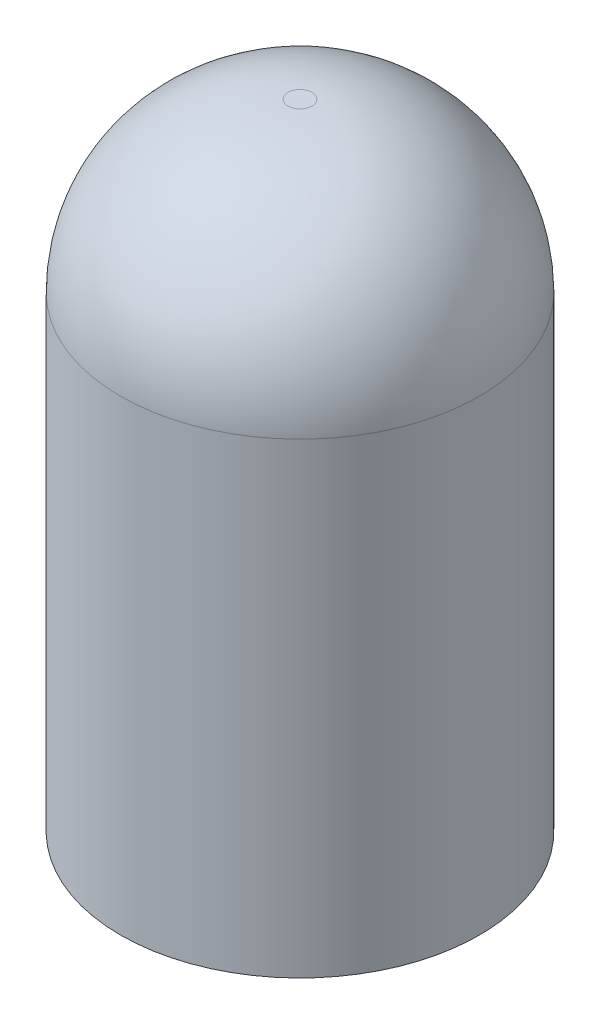
SolidWorks part; units mm, degrees
ref_plane "Front Plane" through (0, 0, 0) normal (0, 0, 1) x (1, 0, 0)
ref_plane "Top Plane" through (0, 0, 0) normal (0, 1, 0) x (1, 0, 0)
ref_plane "Right Plane" through (0, 0, 0) normal (1, 0, 0) x (0, 0, -1)
sketch "Sketch2" plane through (0, 0, 0) normal (0, 1, 0) x (1, 0, 0)
  circle A0 centre (0, 0) radius 1.5
extrude "Boss-Extrude1" add sketch "Sketch2" along normal blind 5.3
fillet "Fillet1" radius 1.4 1 edges at (0, 5.3, 1.5)
sketch "Sketch3" plane through (0, 0, 0) normal (0, 0, 1) x (1, 0, 0)
  line L0 (0, 0) -> (0, 2.6) construction
  line L1 (-1.45, 2.6) -> (1.45, 2.6) construction
  line L2 (-1.45, 2.6) -> (-1.45, 0)
  line L3 (-1.5, 0) -> (1.5, 0) construction
  line L4 (-1.45, 0) -> (-0.9, 0)
  line L5 (-0.9, 0) -> (-0.9, 0.6)
  line L6 (-0.9, 0.6) -> (-0.6241, 0.6)
  line L7 (-0.6241, 0.6) -> (-0.6241, 0.825)
  line L8 (-0.6241, 0.825) -> (-1.2254, 2.6)
  line L9 (-1.2254, 2.6) -> (-1.45, 2.6)
  line L10 (1.45, 2.6) -> (-0.8725, 2.6)
  line L11 (-0.8725, 2.6) -> (0.4967, 0.6)
  line L12 (0.4967, 0.6) -> (0.9, 0.6)
  line L13 (0.9, 0.6) -> (0.9, 0)
  line L14 (0.9, 0) -> (1.45, 0)
  line L15 (1.45, 0) -> (1.45, 2.6)
  line L16 (-0.6241, 0.6) -> (0.4967, 0.6) construction
  line L17 (-0.0637, 0.6) -> (-0.0637, 0) construction
  point P6 (0, 2.6)
extrude "Boss-Extrude2" add sketch "Sketch3" along normal blind 0.25 and the other way blind 0.25 separate body
sketch "Sketch4" plane through (0, 0, 0) normal (0, -1, 0) x (-1, 0, 0)
  line L1 (1.45, -0.25) -> (0.9, -0.25)
  line L2 (1.45, -0.25) -> (1.45, 0.25)
  line L3 (1.45, 0.25) -> (0.9, 0.25)
  line L4 (0.9, -0.25) -> (0.9, 0.25)
  line L5 (-0.9, -0.25) -> (-1.45, -0.25)
  line L6 (-0.9, -0.25) -> (-0.9, 0.25)
  line L7 (-0.9, 0.25) -> (-1.45, 0.25)
  line L8 (-1.45, -0.25) -> (-1.45, 0.25)
  circle A0 centre (-1.175, 0) radius 0.2
  circle A1 centre (1.175, 0) radius 0.2
  dimension "D1" = 0.4
  dimension "D2" = 0.4
extrude "Boss-Extrude3" add sketch "Sketch4" along normal blind 0.05 contours A1 | A0 region at (1.175, 0, 0) region at (-1.175, 0, 0)
